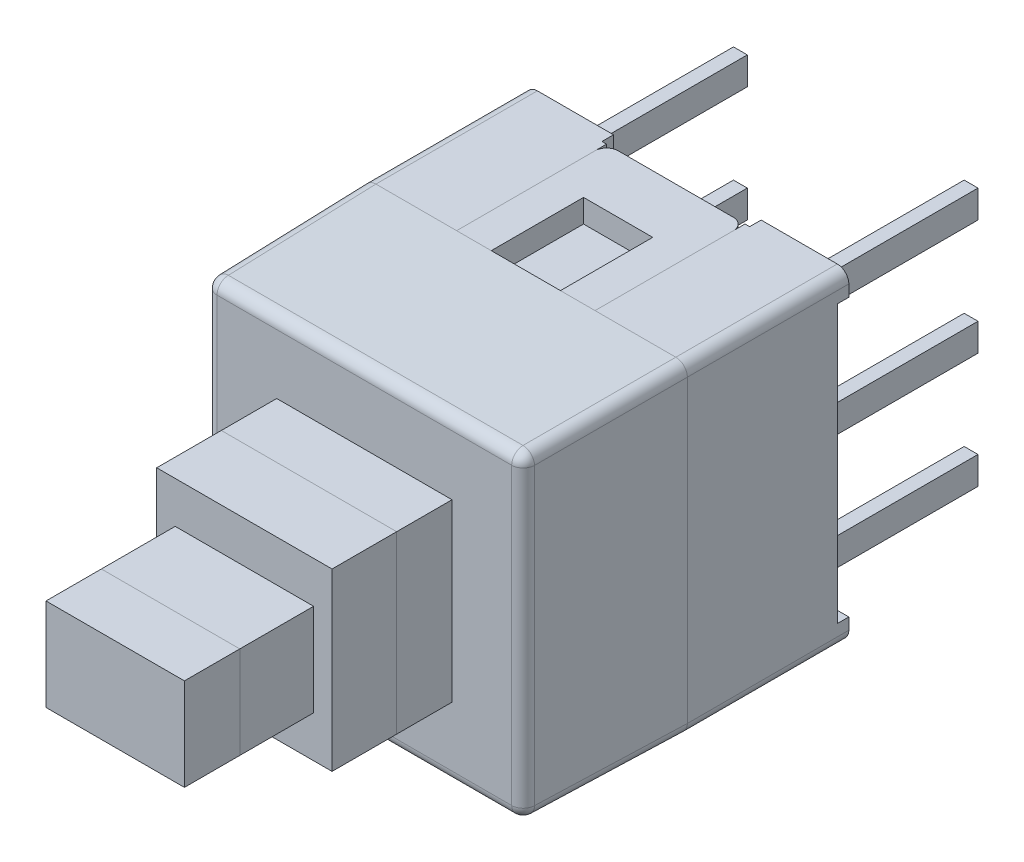
SolidWorks part; units mm, degrees
ref_plane "Plan de face" through (0, 0, 0) normal (0, 0, 1) x (1, 0, 0)
ref_plane "Plan de dessus" through (0, 0, 0) normal (0, 1, 0) x (1, 0, 0)
ref_plane "Plan de droite" through (0, 0, 0) normal (1, 0, 0) x (0, 0, -1)
sketch "Esquisse1" plane through (0, 0, 0) normal (0, 0, 1) x (1, 0, 0)
  line L1 (-3.5, -3.5) -> (3.5, -3.5)
  line L2 (-3.5, -3.5) -> (-3.5, 3.5)
  line L3 (-3.5, 3.5) -> (3.5, 3.5)
  line L4 (3.5, -3.5) -> (3.5, 3.5)
  line L5 (-3.5, -3.5) -> (3.5, 3.5) construction
  line L6 (-3.5, 3.5) -> (3.5, -3.5) construction
  point P0 (0, 0)
  dimension "D1" = 7
extrude "Boss.-Extru.1" add sketch "Esquisse1" along normal blind 3.5
sketch "Esquisse2" plane through (0, 0, 0) normal (0, 0, -1) x (-1, 0, 0)
  line L1 (-3.5, 3.5) -> (-1.6, 3.5)
  line L2 (-3.5, 3.5) -> (-3.5, 3)
  line L3 (-3.5, 3) -> (-1.6, 3)
  line L4 (-1.6, 3.5) -> (-1.6, 3)
  line L5 (3.5, 3.5) -> (1.6, 3.5)
  line L6 (3.5, 3.5) -> (3.5, 3)
  line L7 (3.5, 3) -> (1.6, 3)
  line L8 (1.6, 3.5) -> (1.6, 3)
  line L9 (3.5, -3.5) -> (1.6, -3.5)
  line L10 (3.5, -3.5) -> (3.5, -3)
  line L11 (3.5, -3) -> (1.6, -3)
  line L12 (1.6, -3.5) -> (1.6, -3)
  line L13 (-3.5, -3.5) -> (-1.6, -3.5)
  line L14 (-3.5, -3.5) -> (-3.5, -3)
  line L15 (-3.5, -3) -> (-1.6, -3)
  line L16 (-1.6, -3.5) -> (-1.6, -3)
  line L20 (-3.5, 3.5) -> (-3.5, -3.5)
  line L21 (-3.5, -3.5) -> (3.5, -3.5)
  line L22 (3.5, -3.5) -> (3.5, 3.5)
  line L23 (3.5, 3.5) -> (-3.5, 3.5)
  line L24 (-3.5, 3.5) -> (-3.5, -3.5)
  line L25 (-3.5, -3.5) -> (3.5, -3.5)
  line L26 (3.5, -3.5) -> (3.5, 3.5)
  line L27 (3.5, 3.5) -> (-3.5, 3.5)
  line M17 (-3.5, 3.5) -> (-3.5, -3.5)
  line M18 (-3.5, -3.5) -> (3.5, -3.5)
  line M19 (3.5, -3.5) -> (3.5, 3.5)
  line M20 (3.5, 3.5) -> (-3.5, 3.5)
  dimension "D1" = 0.5
  dimension "D2" = 1.9
  dimension "D3" = 0
extrude "Enlèv. mat.-Extru.1" cut sketch "Esquisse2" against normal blind 0.25 contours L16 L12 L11 L7 L8 L4 L3 L15 M18 M19 M20 M17 region at (0, 0, 0)
sketch "Esquisse3" plane through (0, 3.5, 0) normal (0, 1, 0) x (1, 0, 0)
  line L0 (-1.5, -0.25) -> (-1.5, -3.5)
  line L1 (-1.5, -0.25) -> (1.5, -0.25)
  line L2 (-1.5, -3.5) -> (1.5, -3.5)
  line L3 (1.5, -0.25) -> (1.5, -3.5)
  line L4 (-1.5, -0.25) -> (1.5, -3.5) construction
  line L5 (-1.5, -3.5) -> (1.5, -0.25) construction
  line L6 (-1.6, -0.25) -> (1.6, -0.25) construction
  line L7 (3.5, -3.5) -> (-3.5, -3.5) construction
  point P1 (0, -1.875)
  dimension "D1" = 3
extrude "Enlèv. mat.-Extru.2" cut sketch "Esquisse3" against normal blind 0.5
extrude "Enlèv. mat.-Extru.3" cut sketch "Esquisse3<2>" along normal blind 0.5 from surface starting at face at (0, -3.5, 0.9375)
sketch "Esquisse3<2>" plane through (0, 3.5, 0) normal (0, 1, 0) x (1, 0, 0) same geometry as "Esquisse3"
sketch "Esquisse4" plane through (0, 0, 3.5) normal (0, 0, 1) x (1, 0, 0)
  line L1 (-3.5, 3.5) -> (3.5, 3.5)
  line L2 (-3.5, 3.5) -> (-3.5, -3.5)
  line L3 (-3.5, -3.5) -> (3.5, -3.5)
  line L4 (3.5, 3.5) -> (3.5, -3.5)
extrude "Boss.-Extru.2" add sketch "Esquisse4" along normal blind 3.5 draft 1 separate body
sketch "Esquisse5" plane through (0, 0, 3.5) normal (0, 0, -1) x (-1, 0, 0)
  line L0 (-1.5, 3) -> (1.5, 3) construction
  line L1 (-1.5, 3.5) -> (1.5, 3.5)
  line L2 (-1.5, 3.5) -> (-1.5, 3)
  line L3 (-1.5, 3) -> (1.5, 3)
  line L4 (1.5, 3.5) -> (1.5, 3)
  line L5 (1.5, -3) -> (1.5, -3.5) construction
  line L6 (-1.5, -3.5) -> (1.5, -3.5)
  line L7 (-1.5, -3.5) -> (-1.5, -3)
  line L8 (-1.5, -3) -> (1.5, -3)
  line L9 (1.5, -3.5) -> (1.5, -3)
extrude "Boss.-Extru.3" add sketch "Esquisse5" along normal blind 3.25
sketch "Esquisse8" plane through (0, 0, 0) normal (0, 1, 0) x (1, 0, 0)
  line L1 (-0.75, -1.5) -> (0.75, -1.5)
  line L2 (-0.75, -1.5) -> (-0.75, -3.5)
  line L3 (-0.75, -3.5) -> (0.75, -3.5)
  line L4 (0.75, -1.5) -> (0.75, -3.5)
  line L5 (-1.5, -3.5) -> (1.5, -3.5) construction
  line L7 (-0.15, -1.5) -> (0.15, -1.5)
  line L8 (-0.15, -1.5) -> (-0.15, -3.5)
  line L9 (-0.15, -3.5) -> (0.15, -3.5)
  line L10 (0.15, -1.5) -> (0.15, -3.5)
  point P4 (0, -3.5)
  point P5 (0, -3.5)
  dimension "D1" = 1.5
  dimension "D2" = 2
  dimension "D3" = 0.3
extrude "Enlèv. mat.-Extru.4" cut sketch "Esquisse8" along normal through all contours L3 L4 L1 L2
extrude "Enlèv. mat.-Extru.5" cut sketch "Esquisse8<3>" against normal through all contours L1 L10 L3 L4 | L8 L1 L2 L3 region at (-0.45, 0, 2.5) region at (0.45, 0, 2.5)
sketch "Esquisse8<3>" plane through (0, 0, 0) normal (0, 1, 0) x (1, 0, 0) same geometry as "Esquisse8"
fillet "Congé1" radius 0.25 4 edges at (-3.5, -3.5, 1.75) (-3.5, 3.5, 1.75) (3.5, -3.5, 1.75) (3.5, 3.5, 1.75)
fillet "Congé2" radius 0.25 4 edges at (3.4695, 3.4695, 5.25) (3.4695, -3.4695, 5.25) (-3.4695, -3.4695, 5.25) (-3.4695, 3.4695, 5.25)
fillet "Congé3" radius 0.25 8 edges at (3.3657, -3.3657, 7) (0, -3.4389, 7) (-3.3657, -3.3657, 7) (-3.4389, 0, 7) (-3.3657, 3.3657, 7) (0, 3.4389, 7) (3.3657, 3.3657, 7) (3.4389, 0, 7)
fillet "Congé4" radius 0.25 4 edges at (-1.5, -3.25, 0.25) (-1.5, 3.25, 0.25) (1.5, 3.25, 0.25) (1.5, -3.25, 0.25)
sketch "Esquisse6" plane through (0, 0, 7) normal (0, 0, 1) x (1, 0, 0)
  line L2 (-1.9, -1.9) -> (1.9, -1.9)
  line L3 (-1.9, -1.9) -> (-1.9, 1.9)
  line L4 (-1.9, 1.9) -> (1.9, 1.9)
  line L5 (1.9, -1.9) -> (1.9, 1.9)
  line L6 (-1.9, -1.9) -> (1.9, 1.9) construction
  line L7 (-1.9, 1.9) -> (1.9, -1.9) construction
  point P0 (0, 0)
  point P2 (0, 0)
  dimension "D1" = 3.8
extrude "Boss.-Extru.4" add sketch "Esquisse6" along normal blind 1.2 separate body
extrude "Boss.-Extru.5" add sketch "Esquisse6<3>" along normal blind 1.4 from surface separate body starting at face at (0, 0, 8.2)
sketch "Esquisse6<3>" plane through (0, 0, 7) normal (0, 0, 1) x (1, 0, 0) same geometry as "Esquisse6"
sketch "Esquisse7" plane through (0, 0, 9.6) normal (0, 0, 1) x (1, 0, 0)
  line L1 (-1.5, -1) -> (1.5, -1)
  line L2 (-1.5, -1) -> (-1.5, 1)
  line L3 (-1.5, 1) -> (1.5, 1)
  line L4 (1.5, -1) -> (1.5, 1)
  line L5 (-1.5, -1) -> (1.5, 1) construction
  line L6 (-1.5, 1) -> (1.5, -1) construction
  point P0 (0, 0)
  dimension "D1" = 3
  dimension "D2" = 2
extrude "Boss.-Extru.6" add sketch "Esquisse7" along normal blind 1.6 and the other way up to surface (2.6 mm away) separate body other way up to face at (0, 0, 7)
extrude "Boss.-Extru.7" add sketch "Esquisse7<2>" along normal blind 1.2 from surface separate body starting at face at (0, 0, 11.2)
sketch "Esquisse7<2>" plane through (0, 0, 9.6) normal (0, 0, 1) x (1, 0, 0) same geometry as "Esquisse7"
sketch "Esquisse9" plane through (0, 0, 0.25) normal (0, 0, -1) x (-1, 0, 0)
  line L0 (0, 0) -> (2.5, 0) construction
  line L1 (0, 0) -> (0, 0.8912) construction
  line L2 (2.35, -2.2) -> (2.35, -2.8)
  line L3 (2.35, -0.3) -> (2.65, -0.3)
  line L4 (2.35, -0.3) -> (2.35, 0.3)
  line L5 (2.35, 0.3) -> (2.65, 0.3)
  line L6 (2.65, -0.3) -> (2.65, 0.3)
  line L7 (2.35, -0.3) -> (2.65, 0.3) construction
  line L8 (2.35, 0.3) -> (2.65, -0.3) construction
  line L9 (2.35, 2.2) -> (2.65, 2.2)
  line L10 (2.35, 2.2) -> (2.35, 2.8)
  line L11 (2.35, 2.8) -> (2.65, 2.8)
  line L12 (2.65, 2.2) -> (2.65, 2.8)
  line L13 (2.35, 2.2) -> (2.65, 2.8) construction
  line L14 (2.35, 2.8) -> (2.65, 2.2) construction
  line L15 (2.35, -2.8) -> (2.65, -2.8)
  line L16 (2.65, -2.2) -> (2.65, -2.8)
  line L17 (2.35, -2.2) -> (2.65, -2.2)
  line L18 (-2.35, 2.8) -> (-2.65, 2.8)
  line L19 (-2.65, 2.2) -> (-2.65, 2.8)
  line L20 (-2.35, 2.2) -> (-2.65, 2.2)
  line L21 (-2.35, 2.2) -> (-2.35, 2.8)
  line L22 (-2.35, 0.3) -> (-2.65, 0.3)
  line L23 (-2.65, -0.3) -> (-2.65, 0.3)
  line L24 (-2.35, -0.3) -> (-2.65, -0.3)
  line L25 (-2.35, -0.3) -> (-2.35, 0.3)
  line L26 (-2.35, -2.2) -> (-2.65, -2.2)
  line L27 (-2.65, -2.2) -> (-2.65, -2.8)
  line L28 (-2.35, -2.8) -> (-2.65, -2.8)
  line L29 (-2.35, -2.2) -> (-2.35, -2.8)
  point P8 (2.5, 2.5)
  dimension "D1" = 0.3
  dimension "D2" = 0.6
  dimension "D3" = 2.5
  dimension "D4" = 2.5
extrude "Boss.-Extru.8" add sketch "Esquisse9" along normal blind 3.9 separate body
